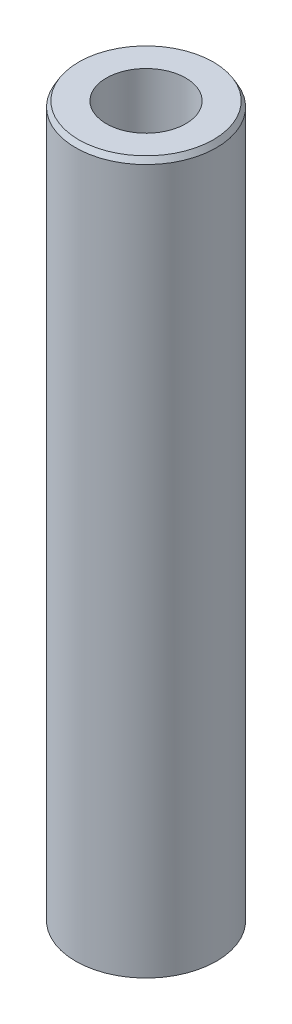
SolidWorks part; units mm, degrees
ref_plane "Front Plane" through (0, 0, 0) normal (0, 0, 1) x (1, 0, 0)
ref_plane "Top Plane" through (0, 0, 0) normal (0, 1, 0) x (1, 0, 0)
ref_plane "Right Plane" through (0, 0, 0) normal (1, 0, 0) x (0, 0, -1)
sketch "Sketch1" plane through (0, 0, 0) normal (0, 1, 0) x (1, 0, 0)
  circle A0 centre (0, 0) radius 35
  dimension "SHAFT_OD" = 70
extrude "Boss-Extrude1" add sketch "Sketch1" along normal blind 354.3285
sketch "Sketch2" plane through (0, 0, 0) normal (0, 1, 0) x (1, 0, 0)
  circle A0 centre (0, 0) radius 19.7233
  dimension "BORE_D" = 39.4466
extrude "Cut-Extrude1" cut sketch "Sketch2" along normal through all
chamfer "Chamfer1" distance 2.6747 angle 30 2 edges at (0, 354.3285, 35) (0, 0, 35) first distance on face at (0, 354.3285, 35) first distance on face at (0, 0, 19.7233)
